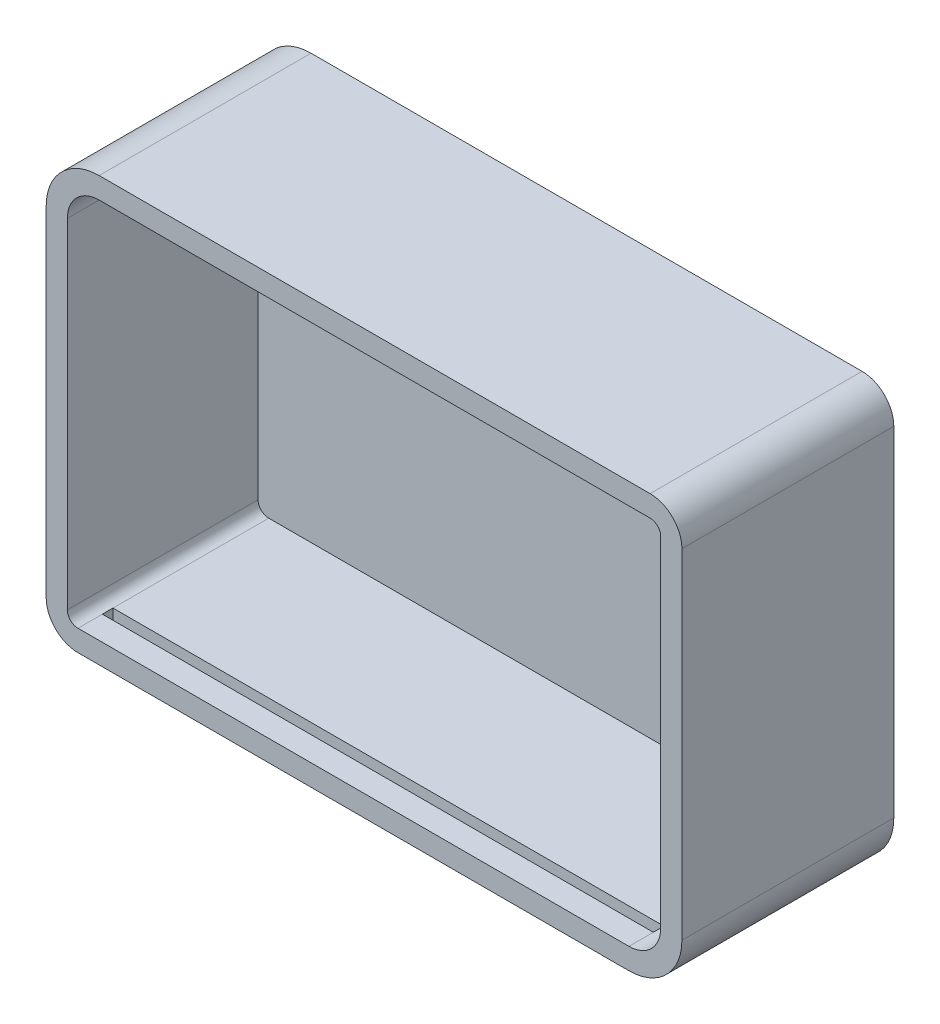
SolidWorks part; units mm, degrees
ref_plane "Front Plane" through (0, 0, 0) normal (0, 0, 1) x (1, 0, 0)
ref_plane "Top Plane" through (0, 0, 0) normal (0, 1, 0) x (1, 0, 0)
ref_plane "Right Plane" through (0, 0, 0) normal (1, 0, 0) x (0, 0, -1)
sketch "Sketch1" plane through (0, 0, 0) normal (0, 0, 1) x (1, 0, 0)
  line L1 (-190.5, -127) -> (190.5, -127)
  line L2 (-190.5, -127) -> (-190.5, 127)
  line L3 (-190.5, 127) -> (190.5, 127)
  line L4 (190.5, -127) -> (190.5, 127)
  line L5 (-190.5, -127) -> (190.5, 127) construction
  line L6 (-190.5, 127) -> (190.5, -127) construction
  point P0 (0, 0)
  dimension "D1" = 381
  dimension "D2" = 254
extrude "Boss-Extrude1" add sketch "Sketch1" against normal blind 127
fillet "Fillet5" radius 19.05 2 edges at (-190.5, -127, -63.5) (190.5, 127, -63.5)
fillet "Fillet4" radius 31.75 2 edges at (190.5, -127, -63.5) (-190.5, 127, -63.5)
sketch "Sketch3" plane through (0, 0, 0) normal (0, 0, -1) x (-1, 0, 0)
  line L16 (-158.75, -114.3) -> (171.45, -114.3)
  line L17 (-177.8, 107.95) -> (-177.8, -95.25)
  line L18 (158.75, 114.3) -> (-171.45, 114.3)
  line L19 (177.8, -107.95) -> (177.8, 95.25)
  line L20 (-158.75, -114.3) -> (171.45, -114.3)
  line L21 (-177.8, 107.95) -> (-177.8, -95.25)
  line L22 (158.75, 114.3) -> (-171.45, 114.3)
  line L23 (177.8, -107.95) -> (177.8, 95.25)
  arc A13 (-177.8, -95.25) -> (-158.75, -114.3) centre (-158.75, -95.25) ccw
  arc A14 (-171.45, 114.3) -> (-177.8, 107.95) centre (-171.45, 107.95) ccw
  arc A15 (177.8, 95.25) -> (158.75, 114.3) centre (158.75, 95.25) ccw
  arc A16 (171.45, -114.3) -> (177.8, -107.95) centre (171.45, -107.95) ccw
  arc A17 (-177.8, -95.25) -> (-158.75, -114.3) centre (-158.75, -95.25) ccw
  arc A18 (-171.45, 114.3) -> (-177.8, 107.95) centre (-171.45, 107.95) ccw
  arc A19 (177.8, 95.25) -> (158.75, 114.3) centre (158.75, 95.25) ccw
  arc A20 (171.45, -114.3) -> (177.8, -107.95) centre (171.45, -107.95) ccw
  dimension "D1" = 12.7
extrude "Cut-Extrude1" cut sketch "Sketch3" along normal offset from surface (114.3 mm away) 12.7 up to face at (0, 0, -127)
sketch "Sketch5" plane through (0, -127, 0) normal (0, -1, 0) x (1, 0, 0)
  line L0 (158.75, -127) -> (158.75, 0) construction
  line L1 (158.75, -14.605) -> (-171.45, -14.605)
  line L2 (158.75, -14.605) -> (158.75, -20.955)
  line L3 (158.75, -20.955) -> (-171.45, -20.955)
  line L4 (-171.45, -14.605) -> (-171.45, -20.955)
  line L5 (-171.45, 0) -> (-171.45, -127) construction
  line L6 (-171.45, 0) -> (158.75, 0) construction
  dimension "D1" = 6.35
  dimension "D2" = 14.605
extrude "Cut-Extrude2" cut sketch "Sketch5" against normal up to next
